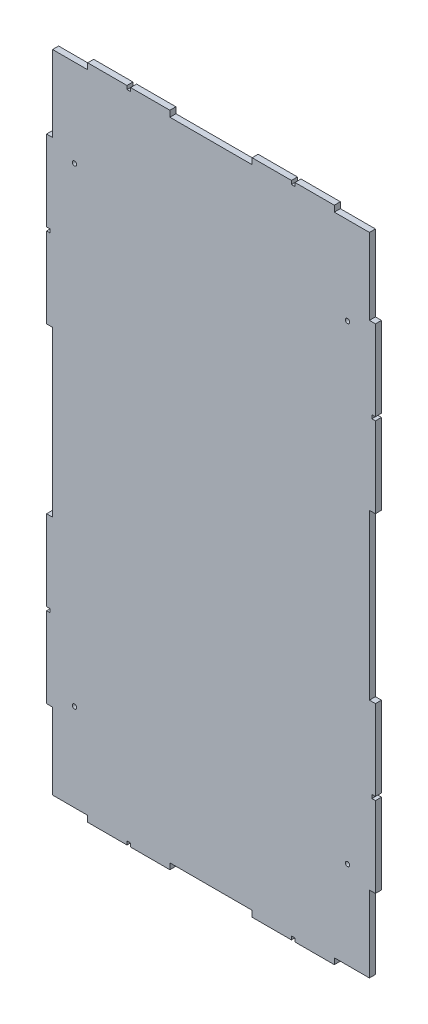
SolidWorks part; units mm, degrees
ref_plane "Front Plane" through (0, 0, 0) normal (0, 0, 1) x (1, 0, 0)
ref_plane "Top Plane" through (0, 0, 0) normal (0, 1, 0) x (1, 0, 0)
ref_plane "Right Plane" through (0, 0, 0) normal (1, 0, 0) x (0, 0, -1)
sketch "Sketch1" plane through (0, 0, 0) normal (0, 0, 1) x (1, 0, 0)
  line L0 (-0.0027, 588.9972) -> (-0.0027, 519.4972)
  line L1 (-0.0027, 519.4972) -> (-5.5027, 519.4972)
  line L2 (-5.5027, 519.4972) -> (-5.5027, 446.1222)
  line L3 (-5.5027, 446.1222) -> (-2.2527, 446.1222)
  line L4 (-2.2527, 446.1222) -> (-2.2527, 444.4972)
  line L5 (-2.2527, 444.4972) -> (-2.2527, 442.8722)
  line L6 (-2.2527, 442.8722) -> (-5.5027, 442.8722)
  line L7 (-5.5027, 442.8722) -> (-5.5027, 369.4972)
  line L8 (-5.5027, 369.4972) -> (-0.0027, 369.4972)
  line L9 (-0.0027, 369.4972) -> (-0.0027, 219.4972)
  line L10 (-0.0027, 219.4972) -> (-5.5027, 219.4972)
  line L11 (-5.5027, 219.4972) -> (-5.5027, 146.1222)
  line L12 (-5.5027, 146.1222) -> (-2.2527, 146.1222)
  line L13 (-2.2527, 146.1222) -> (-2.2527, 144.4972)
  line L14 (-2.2527, 144.4972) -> (-2.2527, 142.8722)
  line L15 (-2.2527, 142.8722) -> (-5.5027, 142.8722)
  line L16 (-5.5027, 142.8722) -> (-5.5027, 69.4972)
  line L17 (-5.5027, 69.4972) -> (-0.0027, 69.4972)
  line L18 (-0.0027, 69.4972) -> (-0.0027, -0.0028)
  line L19 (-0.0027, -0.0028) -> (31.9973, -0.0028)
  line L20 (31.9973, -0.0028) -> (31.9973, -5.5028)
  line L21 (31.9973, -5.5028) -> (67.8723, -5.5028)
  line L22 (67.8723, -5.5028) -> (67.8723, -2.2528)
  line L23 (67.8723, -2.2528) -> (69.4973, -2.2528)
  line L24 (69.4973, -2.2528) -> (71.1223, -2.2528)
  line L25 (71.1223, -2.2528) -> (71.1223, -5.5028)
  line L26 (71.1223, -5.5028) -> (106.9973, -5.5028)
  line L27 (106.9973, -5.5028) -> (106.9973, -0.0028)
  line L28 (106.9973, -0.0028) -> (181.9973, -0.0028)
  line L29 (181.9973, -0.0028) -> (181.9973, -5.5028)
  line L30 (181.9973, -5.5028) -> (217.8723, -5.5028)
  line L31 (217.8723, -5.5028) -> (217.8723, -2.2528)
  line L32 (217.8723, -2.2528) -> (219.4973, -2.2528)
  line L33 (219.4973, -2.2528) -> (221.1223, -2.2528)
  line L34 (221.1223, -2.2528) -> (221.1223, -5.5028)
  line L35 (221.1223, -5.5028) -> (256.9973, -5.5028)
  line L36 (256.9973, -5.5028) -> (256.9973, -0.0028)
  line L37 (256.9973, -0.0028) -> (288.9973, -0.0028)
  line L38 (288.9973, -0.0028) -> (288.9973, 69.4972)
  line L39 (288.9973, 69.4972) -> (294.4973, 69.4972)
  line L40 (294.4973, 69.4972) -> (294.4973, 142.8722)
  line L41 (294.4973, 142.8722) -> (291.2473, 142.8722)
  line L42 (291.2473, 142.8722) -> (291.2473, 144.4972)
  line L43 (291.2473, 144.4972) -> (291.2473, 146.1222)
  line L44 (291.2473, 146.1222) -> (294.4973, 146.1222)
  line L45 (294.4973, 146.1222) -> (294.4973, 219.4972)
  line L46 (294.4973, 219.4972) -> (288.9973, 219.4972)
  line L47 (288.9973, 219.4972) -> (288.9973, 369.4972)
  line L48 (288.9973, 369.4972) -> (294.4973, 369.4972)
  line L49 (294.4973, 369.4972) -> (294.4973, 442.8722)
  line L50 (294.4973, 442.8722) -> (291.2473, 442.8722)
  line L51 (291.2473, 442.8722) -> (291.2473, 444.4972)
  line L52 (291.2473, 444.4972) -> (291.2473, 446.1222)
  line L53 (291.2473, 446.1222) -> (294.4973, 446.1222)
  line L54 (294.4973, 446.1222) -> (294.4973, 519.4972)
  line L55 (294.4973, 519.4972) -> (288.9973, 519.4972)
  line L56 (288.9973, 519.4972) -> (288.9973, 588.9972)
  line L57 (288.9973, 588.9972) -> (256.9973, 588.9972)
  line L58 (256.9973, 588.9972) -> (256.9973, 594.4972)
  line L59 (256.9973, 594.4972) -> (221.1223, 594.4972)
  line L60 (221.1223, 594.4972) -> (221.1223, 591.2472)
  line L61 (221.1223, 591.2472) -> (219.4973, 591.2472)
  line L62 (219.4973, 591.2472) -> (217.8723, 591.2472)
  line L63 (217.8723, 591.2472) -> (217.8723, 594.4972)
  line L64 (217.8723, 594.4972) -> (181.9973, 594.4972)
  line L65 (181.9973, 594.4972) -> (181.9973, 588.9972)
  line L66 (181.9973, 588.9972) -> (106.9973, 588.9972)
  line L67 (106.9973, 588.9972) -> (106.9973, 594.4972)
  line L68 (106.9973, 594.4972) -> (71.1223, 594.4972)
  line L69 (71.1223, 594.4972) -> (71.1223, 591.2472)
  line L70 (71.1223, 591.2472) -> (69.4973, 591.2472)
  line L71 (69.4973, 591.2472) -> (67.8723, 591.2472)
  line L72 (67.8723, 591.2472) -> (67.8723, 594.4972)
  line L73 (67.8723, 594.4972) -> (31.9973, 594.4972)
  line L74 (31.9973, 594.4972) -> (31.9973, 588.9972)
  line L75 (31.9973, 588.9972) -> (-0.0027, 588.9972)
sketch "Sketch2" plane through (0, 0, 0) normal (0, 0, 1) x (1, 0, 0)
  line L0 (181.9973, 588.9972) -> (106.9973, 588.9972) construction
  line L1 (19.9973, 508.9972) -> (268.9973, 508.9972)
  line L2 (19.9973, 508.9972) -> (19.9973, 79.9972)
  line L3 (19.9973, 79.9972) -> (268.9973, 79.9972)
  line L4 (268.9973, 508.9972) -> (268.9973, 79.9972)
  line L5 (-0.0027, 588.9972) -> (-0.0027, 519.4972) construction
  line L6 (-0.0027, 369.4972) -> (-0.0027, 219.4972) construction
  circle A0 centre (19.9973, 508.9972) radius 2
  circle A1 centre (268.9973, 508.9972) radius 2
  circle A2 centre (268.9973, 79.9972) radius 2
  circle A3 centre (19.9973, 79.9972) radius 2
  point P12 (144.4973, 508.9972)
  point P13 (144.4973, 588.9972)
  point P14 (19.9973, 294.4972)
  point P17 (-0.0027, 294.4972)
  dimension "D3" = 4
  dimension "D1" = 80
  dimension "D2" = 20
extrude "Boss-Extrude1" add sketch "Sketch1" along normal blind 5.5
extrude "Cut-Extrude1" cut sketch "Sketch2" against normal through all and the other way through all contours L4 A1 L1 | L1 A1 L4 | L2 A0 L1 | L1 A0 L2 | L2 A3 L3 | L3 A3 L2 | L3 A2 L4 | L4 A2 L3 region at (19.7144, 509.2801, 0) region at (20.8461, 508.1484, 0) region at (269.2803, 509.2801, 0) region at (268.1485, 508.1484, 0) region at (20.8461, 80.846, 0) region at (19.7144, 79.7143, 0) region at (269.2803, 79.7143, 0) region at (268.1485, 80.846, 0)
